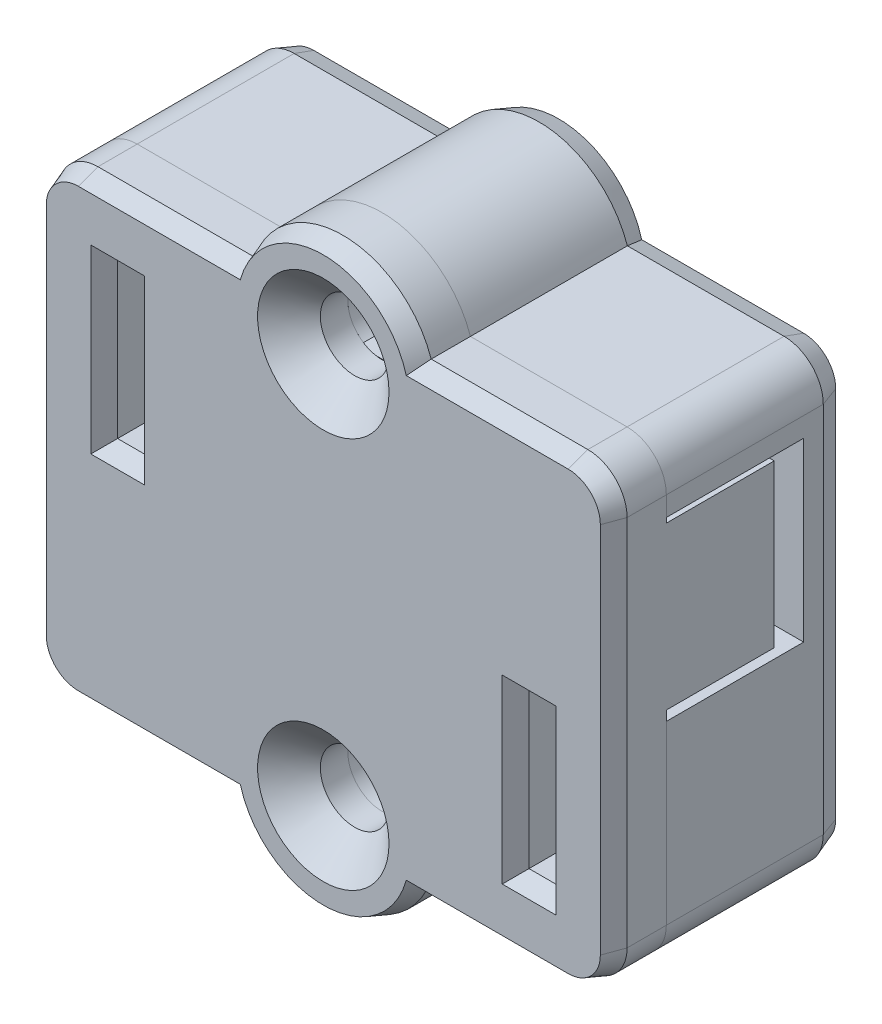
SolidWorks part; units mm, degrees
ref_plane "Спереди" through (0, 0, 0) normal (0, 0, 1) x (1, 0, 0)
ref_plane "Сверху" through (0, 0, 0) normal (0, 1, 0) x (1, 0, 0)
ref_plane "Справа" through (0, 0, 0) normal (1, 0, 0) x (0, 0, -1)
sketch "Sketch2" plane through (0, 0, 0) normal (0, 0, 1) x (1, 0, 0)
  line L1 (8.9024, -9.7858) -> (10.9024, -9.7858)
  line L2 (8.9024, -9.7858) -> (8.9024, -1.7858)
  line L3 (8.9024, -1.7858) -> (10.9024, -1.7858)
  line L4 (10.9024, -9.7858) -> (10.9024, -1.7858)
  line L5 (-10.0691, -0.7858) -> (-12.0691, -0.7858)
  line L6 (-10.0691, -0.7858) -> (-10.0691, 7.2142)
  line L7 (-10.0691, 7.2142) -> (-12.0691, 7.2142)
  line L8 (-12.0691, -0.7858) -> (-12.0691, 7.2142)
  dimension "D1" = 8
  dimension "D2" = 8
  dimension "D5" = 2
  dimension "D6" = 2
sketch "Sketch4" plane through (0, 0, 0) normal (0, 0, 1) x (1, 0, 0)
  line L0 (13.9024, 10.2142) -> (3.9167, 10.2142)
  line L1 (10.9024, -9.7858) -> (0.3699, -9.7858)
  line L2 (10.9024, -9.7858) -> (10.9024, 7.2142)
  line L3 (10.9024, 7.2142) -> (0.3699, 7.2142)
  line L4 (-12.0691, -9.7858) -> (-12.0691, 7.2142)
  line L5 (-15.0691, -12.7858) -> (-15.0691, 10.2142)
  line L6 (13.9024, -12.7858) -> (3.9167, -12.7858)
  line L7 (13.9024, -12.7858) -> (13.9024, 10.2142)
  line L8 (-0.5833, -11.1954) -> (-0.5833, 8.6818) construction
  line L9 (-12.0691, -1.2858) -> (-6.8964, -1.2858) construction
  line L10 (-1.5366, 7.2142) -> (-12.0691, 7.2142)
  line L11 (-5.0833, 10.2142) -> (-15.0691, 10.2142)
  line L12 (13.9024, 10.2142) -> (-15.0691, 10.2142) construction
  line L13 (-5.0833, -12.7858) -> (-15.0691, -12.7858)
  line L14 (13.9024, -12.7858) -> (-15.0691, -12.7858) construction
  line L15 (10.9024, 7.2142) -> (-12.0691, 7.2142) construction
  line L16 (-1.5366, -9.7858) -> (-12.0691, -9.7858)
  line L17 (10.9024, -9.7858) -> (-12.0691, -9.7858) construction
  arc A0 (0.3699, -9.7858) -> (-1.5366, -9.7858) centre (-0.5833, -11.2534) cw
  arc A1 (3.9167, 10.2142) -> (-5.0833, 10.2142) centre (-0.5833, 8.6818) ccw
  arc A2 (0.3699, 7.2142) -> (-1.5366, 7.2142) centre (-0.5833, 8.6818) ccw
  arc A3 (3.9167, -12.7858) -> (-5.0833, -12.7858) centre (-0.5833, -11.2534) cw
  point P12 (-0.5833, -1.2858)
  dimension "D2" = 3.5
  dimension "D1" = 3
extrude "Extrude3" add sketch "Sketch4" along normal blind 7
sketch "Sketch5" plane through (0, 7.2142, 0) normal (0, -1, 0) x (1, 0, 0)
  line L0 (-12.0691, 7) -> (-12.0691, 0) construction
  line L5 (0.3699, 7) -> (0.3699, 0)
  line L6 (0.3699, 0) -> (10.9024, 0)
  line L7 (10.9024, 0) -> (10.9024, 7)
  line L8 (-12.0691, 0) -> (10.9024, 0)
  line L9 (-12.0691, 7) -> (-12.0691, 0)
  line L10 (10.9024, 7) -> (0.3699, 7)
  line L11 (10.9024, 7) -> (-12.0691, 7)
  arc A0 (-12.0691, 7) -> (-5.0691, 0) centre (-5.0691, 7) ccw
  line M10 (0.3699, 0) -> (10.9024, 0)
  dimension "D1" = 0
extrude "Extrude4" add sketch "Sketch5" along normal blind 8 contours A0 M10 region at (-10.5055, 7.2142, 1.5636)
sketch "Sketch6" plane through (0, -9.7858, 0) normal (0, 1, 0) x (1, 0, 0)
  line L1 (10.9024, -7) -> (10.9024, 0) construction
  line L5 (0.3699, 0) -> (0.3699, -7)
  line L6 (10.9024, 0) -> (0.3699, 0)
  line L7 (0.3699, 0) -> (0.3699, -7)
  line L8 (10.9024, 0) -> (0.3699, 0)
  line L9 (10.9024, -7) -> (10.9024, 0)
  line L10 (0.3699, -7) -> (10.9024, -7)
  line L11 (0.3699, -7) -> (10.9024, -7)
  line L13 (10.9024, -7) -> (10.9024, 0)
  arc A0 (10.9024, -7) -> (3.9024, 0) centre (3.9024, -7) ccw
  line M8 (10.9024, -7) -> (10.9024, 0)
  line M10 (10.9024, 0) -> (0.3699, 0)
  dimension "D1" = 0
extrude "Extrude5" add sketch "Sketch6" along normal blind 8 contours A0 M8 M10 region at (9.3389, -9.7858, 1.5636)
sketch "Sketch7" plane through (0, 0, 0) normal (0, 0, -1) x (-1, 0, 0)
  line L6 (-13.9024, 10.2142) -> (-13.9024, -12.7858)
  line L7 (-13.9024, -12.7858) -> (-3.9167, -12.7858)
  line L8 (5.0833, -12.7858) -> (15.0691, -12.7858)
  line L9 (15.0691, -12.7858) -> (15.0691, 10.2142)
  line L10 (15.0691, 10.2142) -> (5.0833, 10.2142)
  line L11 (-3.9167, 10.2142) -> (-13.9024, 10.2142)
  line L12 (-13.9024, 10.2142) -> (-13.9024, -12.7858)
  line L13 (-13.9024, -12.7858) -> (-3.9167, -12.7858)
  line L14 (5.0833, -12.7858) -> (15.0691, -12.7858)
  line L15 (15.0691, -12.7858) -> (15.0691, 10.2142)
  line L16 (15.0691, 10.2142) -> (5.0833, 10.2142)
  line L17 (-3.9167, 10.2142) -> (-13.9024, 10.2142)
  circle A0 centre (0.5833, 8.6818) radius 1.75 construction
  circle A1 centre (0.5833, 8.6818) radius 1.75
  arc A2 (-3.9167, -12.7858) -> (5.0833, -12.7858) centre (0.5833, -11.2534) ccw
  arc A3 (5.0833, 10.2142) -> (-3.9167, 10.2142) centre (0.5833, 8.6818) ccw
  arc A4 (-3.9167, -12.7858) -> (5.0833, -12.7858) centre (0.5833, -11.2534) ccw
  arc A5 (5.0833, 10.2142) -> (-3.9167, 10.2142) centre (0.5833, 8.6818) ccw
  arc A7 (-0.3699, -9.7858) -> (1.5366, -9.7858) centre (0.5833, -11.2534) ccw construction
  circle A8 centre (0.5833, -11.2534) radius 1.75
  dimension "D1" = 0
extrude "Extrude6" add sketch "Sketch7" along normal blind 2
fillet "Fillet1" radius 2 4 edges at (-15.0691, -12.7858, 2.5) (13.9024, -12.7858, 2.5) (13.9024, 10.2142, 2.5) (-15.0691, 10.2142, 2.5)
sketch "Sketch9" plane through (-12.0691, 0, 0) normal (1, 0, 0) x (0, 0, -1)
  line L0 (0, -0.7858) -> (0, -9.7858)
  line L1 (0, -0.7858) -> (-7, -0.7858)
  line L3 (-7, -0.7858) -> (-7, -9.7858)
  line L4 (-7, -9.7858) -> (0, -9.7858)
extrude "Extrude8" cut sketch "Sketch9" against normal up to next contours L3 L4 L0 L1
sketch "Sketch10" plane through (10.9024, 0, 0) normal (-1, 0, 0) x (0, 0, 1)
  line L4 (0, -1.7858) -> (7, -1.7858)
  line L5 (7, -1.7858) -> (7, 7.2142)
  line L6 (7, 7.2142) -> (0, 7.2142)
  line L7 (0, 7.2142) -> (0, -1.7858)
  line L8 (0, -1.7858) -> (7, -1.7858)
  line L9 (7, -1.7858) -> (7, 7.2142)
  line L10 (7, 7.2142) -> (0, 7.2142)
  line L11 (0, 7.2142) -> (0, -1.7858)
  dimension "D1" = 0
extrude "Extrude9" cut sketch "Sketch10" against normal up to next
sketch "Sketch11" plane through (0, 7.2142, 0) normal (0, -1, 0) x (1, 0, 0)
  line L0 (13.9024, 0) -> (0.3699, 0) construction
  line L1 (3.9167, 7) -> (-5.0833, 7) construction
  line L2 (-0.5833, 1.9408) -> (3.0586, 1.9408)
  line L3 (3.0586, 1.9408) -> (3.0586, 0)
  line L4 (-4.2253, 0) -> (3.0586, 0)
  line L5 (0.3699, 0) -> (13.9024, 0)
  line L6 (13.9024, 0) -> (13.9024, 7)
  line L7 (13.9024, 7) -> (0.3699, 7)
  line L12 (0.3699, 7) -> (0.3699, 0)
  line L13 (0.3699, 7) -> (0.3699, 0)
  arc A0 (-4.2253, 0) -> (-0.5833, 1.9408) centre (-0.5833, -2.4468) cw
  point P7 (-0.5833, 7)
  dimension "D1" = 0
extrude "Extrude10" add sketch "Sketch11" along normal up to vertex (8 mm away) contours A0 L2 L3 L4 up to point (-5.0691, -0.7858, 0)
sketch "Sketch12" plane through (0, -9.7858, 0) normal (0, 1, 0) x (1, 0, 0)
  line L0 (-4.2253, 0) -> (-4.2253, -1.9408)
  line L1 (-4.2253, -1.9408) -> (-0.5833, -1.9408)
  line L2 (-4.2253, 0) -> (3.0586, 0)
  arc A0 (-4.2253, 0) -> (-0.5833, -1.9408) centre (-0.5833, 2.4468) ccw construction
  arc A1 (-0.5833, -1.9408) -> (3.0586, 0) centre (-1.4942, 4.1561) ccw
extrude "Extrude11" add sketch "Sketch12" along normal up to vertex (8 mm away) up to point (3.9024, -1.7858, 0)
sketch "Sketch13" plane through (0, -0.7858, 0) normal (0, -1, 0) x (1, 0, 0)
  line L3 (-4.2253, 0) -> (3.0586, 0)
  line L4 (3.0586, 0) -> (3.0586, 1.9408)
  line L5 (3.0586, 1.9408) -> (-0.5833, 1.9408)
  line L6 (-4.2253, 0) -> (3.0586, 0)
  line L7 (3.0586, 0) -> (3.0586, 1.9408)
  line L8 (3.0586, 1.9408) -> (-0.5833, 1.9408)
  arc A0 (-0.5833, 1.9408) -> (3.0586, 0) centre (-0.5833, -2.4468) cw
  arc A1 (-0.5833, 1.9408) -> (-4.2253, 0) centre (-0.5833, -2.4468) ccw
  arc A2 (-0.5833, 1.9408) -> (-4.2253, 0) centre (-0.5833, -2.4468) ccw
  arc M5 (-0.5833, 1.9408) -> (-4.2253, 0) centre (-0.5833, -2.4468) ccw
  line M6 (-4.2253, 0) -> (3.0586, 0)
  dimension "D1" = 0
extrude "Extrude12" add sketch "Sketch13" along normal up to vertex (1 mm away) contours A0 M5 M6 region at (-0.5833, -0.7858, 0.7932) up to point (3.0586, -1.7858, 0)
sketch "Sketch14" plane through (0, -9.7858, 0) normal (0, 1, 0) x (1, 0, 0)
  line L20 (-15.0691, -1.5) -> (-15.0691, -7)
  line L21 (-15.0691, -7) -> (9.4024, -7)
  line L28 (3.9024, -1.5) -> (3.6781, -1.5)
  line L29 (-6.8681, -1.5) -> (-15.0691, -1.5)
  line L30 (-5.7253, -3.4408) -> (-6.8681, -1.5)
  line L31 (-0.478, -3.4408) -> (-5.7253, -3.4408)
  arc A11 (9.4024, -7) -> (3.9024, -1.5) centre (3.9024, -7) ccw
  arc A12 (-0.478, -3.4408) -> (3.6781, -1.5) centre (-1.4942, 4.1561) ccw
extrude "Extrude13" add sketch "Sketch14" along normal blind 8.25 from offset 0.25 separate body
sketch "Sketch15" plane through (0, 7.2142, 0) normal (0, -1, 0) x (1, 0, 0)
  line L28 (-10.5691, 7) -> (13.9024, 7)
  line L29 (13.9024, 7) -> (13.9024, 1.5)
  line L36 (13.9024, 1.5) -> (4.5586, 1.5)
  line L37 (4.5586, 1.5) -> (4.5586, 3.4408)
  line L38 (4.5586, 3.4408) -> (-0.5833, 3.4408)
  line L39 (-4.9521, 1.5) -> (-5.0691, 1.5)
  arc A26 (-0.5833, 3.4408) -> (-4.9521, 1.5) centre (-0.5833, -2.4468) ccw
  arc A27 (-10.5691, 7) -> (-5.0691, 1.5) centre (-5.0691, 7) ccw
extrude "Extrude14" add sketch "Sketch15" along normal blind 8.25 from offset 0.25
sketch "Sketch16" plane through (0, 0, 7) normal (0, 0, 1) x (1, 0, 0)
  line L0 (-15.0691, 8.2142) -> (-15.0691, -10.7858)
  line L1 (13.9024, 8.2142) -> (13.9024, -10.7858)
  line L5 (-10.5691, -1.2858) -> (-12.0691, -1.2858)
  line L6 (-10.5691, -1.2858) -> (-10.5691, 7.2142)
  line L7 (0.3699, 7.2142) -> (13.9024, 7.2142)
  line L8 (13.9024, 7.2142) -> (13.9024, 8.2142)
  line L9 (11.9024, 10.2142) -> (3.9167, 10.2142)
  line L10 (-5.0833, 10.2142) -> (-13.0691, 10.2142)
  line L11 (-15.0691, 8.2142) -> (-15.0691, -0.7858)
  line L12 (-15.0691, -0.7858) -> (-12.0691, -0.7858)
  line L13 (-12.0691, -0.7858) -> (-12.0691, 7.2142)
  line L14 (-10.5691, 7.2142) -> (-12.0691, 7.2142)
  line L16 (11.9024, 10.2142) -> (3.9167, 10.2142)
  line L17 (-5.0833, 10.2142) -> (-13.0691, 10.2142)
  line L21 (13.9024, -1.7858) -> (10.9024, -1.7858)
  line L22 (10.9024, -1.7858) -> (10.9024, -9.7858)
  line L23 (10.9024, -9.7858) -> (0.3699, -9.7858)
  line L24 (-15.0691, -9.7858) -> (-15.0691, -10.7858)
  line L25 (-13.0691, -12.7858) -> (-5.0833, -12.7858)
  line L26 (3.9167, -12.7858) -> (11.9024, -12.7858)
  line L27 (13.9024, -10.7858) -> (13.9024, -1.7858)
  line L28 (-12.0691, -1.2858) -> (-12.0691, 7.2142)
  line L29 (9.4024, -1.2858) -> (9.4024, -9.5358) construction
  line L30 (9.4024, -1.2858) -> (10.9024, -1.2858)
  line L32 (-13.0691, -12.7858) -> (-5.0833, -12.7858)
  line L33 (3.9167, -12.7858) -> (11.9024, -12.7858)
  line L35 (9.4024, -1.2858) -> (9.4024, -9.7858)
  line L36 (9.4024, -9.7858) -> (10.9024, -9.7858)
  line L37 (10.9024, -1.2858) -> (10.9024, -9.7858)
  line L41 (-1.5366, -9.7858) -> (-15.0691, -9.7858)
  line L44 (-12.0691, 7.2142) -> (-1.5366, 7.2142)
  line L45 (-12.0691, 7.2142) -> (-1.5366, 7.2142)
  circle A0 centre (-0.5833, 8.6818) radius 1.75 construction
  circle A1 centre (-0.5833, 8.6818) radius 1.75
  arc A3 (13.9024, 8.2142) -> (11.9024, 10.2142) centre (11.9024, 8.2142) ccw
  arc A4 (3.9167, 10.2142) -> (-5.0833, 10.2142) centre (-0.5833, 8.6818) ccw
  arc A5 (-13.0691, 10.2142) -> (-15.0691, 8.2142) centre (-13.0691, 8.2142) ccw
  arc A6 (13.9024, 8.2142) -> (11.9024, 10.2142) centre (11.9024, 8.2142) ccw
  arc A7 (3.9167, 10.2142) -> (-5.0833, 10.2142) centre (-0.5833, 8.6818) ccw
  arc A8 (-13.0691, 10.2142) -> (-15.0691, 8.2142) centre (-13.0691, 8.2142) ccw
  arc A9 (-15.0691, -10.7858) -> (-13.0691, -12.7858) centre (-13.0691, -10.7858) ccw
  arc A10 (-1.5366, -9.7858) -> (0.3699, -9.7858) centre (-0.5833, -11.2534) ccw
  arc A11 (11.9024, -12.7858) -> (13.9024, -10.7858) centre (11.9024, -10.7858) ccw
  arc A12 (-15.0691, -10.7858) -> (-13.0691, -12.7858) centre (-13.0691, -10.7858) ccw
  arc A13 (-1.5366, -9.7858) -> (0.3699, -9.7858) centre (-0.5833, -11.2534) ccw
  arc A14 (11.9024, -12.7858) -> (13.9024, -10.7858) centre (11.9024, -10.7858) ccw
  circle A15 centre (-0.5833, -11.2534) radius 1.75
  arc A20 (0.3699, 7.2142) -> (-1.5366, 7.2142) centre (-0.5833, 8.6818) ccw
  arc A21 (0.3699, 7.2142) -> (-1.5366, 7.2142) centre (-0.5833, 8.6818) ccw
  arc A22 (-5.0833, -12.7858) -> (3.9167, -12.7858) centre (-0.5833, -11.2534) ccw
  arc A23 (-5.0833, -12.7858) -> (3.9167, -12.7858) centre (-0.5833, -11.2534) ccw
  line M21 (-15.0691, -9.5358) -> (9.4024, -9.5358)
  line M22 (9.4024, -9.5358) -> (9.4024, -1.2858)
  line M23 (9.4024, -1.2858) -> (13.9024, -1.2858)
  line M24 (13.9024, -1.2858) -> (13.9024, 6.9642)
  line M25 (13.9024, 6.9642) -> (-10.5691, 6.9642)
  line M26 (-10.5691, 6.9642) -> (-10.5691, -1.2858)
  line M27 (-10.5691, -1.2858) -> (-15.0691, -1.2858)
  line M28 (-15.0691, -1.2858) -> (-15.0691, -9.5358)
  dimension "D1" = 0
  dimension "D2" = 0
extrude "Extrude15" add sketch "Sketch16" along normal blind 3 contours L17 A8 L0 L28 L14 L45 A1 L1 A6 L16 A7 M27 M25 | L32 A23 L33 A14 L1 L37 L36 L35 A15 A13 L0 A12 M23 M21 | A15 A1 M21 M22 M23 M24 M25 M26 M27 M28 | A1 L45 L6 M25 region at (-3.1563, 8.1031, 7) region at (-13.5691, -1.0358, 7) region at (-0.5833, -1.2858, 7) region at (-8.1758, -9.6599, 7) region at (1.9897, -10.6747, 7) region at (-5.9253, 7.0879, 7) region at (4.7586, -9.6595, 7) region at (7.0091, 7.0883, 7) region at (12.4024, -1.5358, 7)
sketch "Sketch18" plane through (0, 0, 10) normal (0, 0, 1) x (1, 0, 0)
  line L1 (-12.0691, -1.2858) -> (-10.0691, -1.2858)
  line L2 (-12.0691, -1.2858) -> (-12.0691, 7.2142)
  line L3 (-12.0691, 7.2142) -> (-10.0691, 7.2142)
  line L4 (-10.0691, -1.2858) -> (-10.0691, 7.2142)
  line L5 (10.9024, -9.7858) -> (8.9024, -9.7858)
  line L6 (10.9024, -9.7858) -> (10.9024, -1.2858)
  line L7 (10.9024, -1.2858) -> (8.9024, -1.2858)
  line L8 (8.9024, -9.7858) -> (8.9024, -1.2858)
  dimension "D1" = 2
  dimension "D2" = 2
extrude "Extrude16" cut sketch "Sketch18" against normal up to next (6.6056 mm away)
chamfer "Chamfer3" distance 1.6 angle 45 2 edges at (1.1667, -11.2534, 10) (1.1667, 8.6818, 10)
chamfer "Chamfer1" distance 1 angle 20 14 edges at (-9.0762, 10.2142, -2) (-14.4833, 9.6284, -2) (-15.0691, -1.2858, -2) (-14.4833, -12.2, -2) (-9.0762, -12.7858, -2) (-0.5833, -16.0072, -2) (7.9095, -12.7858, -2) (13.3166, -12.2, -2) (13.9024, -1.2858, -2) (13.3166, 9.6284, -2) (7.9095, 10.2142, -2) (-0.5833, 13.4356, -2) (-2.3333, 8.6818, -2) (-2.3333, -11.2534, -2) first distance on face at (-9.0762, 10.2142, 2.5) first distance on face at (-14.2762, 9.4213, 2.5) first distance on face at (-15.0691, -3.2858, 3) first distance on face at (-14.2762, -11.9929, 2.5) first distance on face at (-9.0762, -12.7858, 2.5) first distance on face at (-0.5833, -14.3965, 2.5) first distance on face at (7.9095, -12.7858, 2.5) first distance on face at (13.1095, -11.9929, 2.5) first distance on face at (13.9024, 0.7142, 3) first distance on face at (13.1095, 9.4213, 2.5) first distance on face at (7.9095, 10.2142, 2.5) first distance on face at (-0.5833, 11.8249, 2.5) first distance on face at (-0.5833, 7.7034, 2.9628) first distance on face at (-0.5833, -10.275, 2.9434)
chamfer "Chamfer2" distance 1 angle 20 20 edges at (-11.0691, 7.2142, 10) (-12.0691, 2.9642, 10) (-10.0691, 2.9642, 10) (-11.0691, -1.2858, 10) (9.9024, -9.7858, 10) (8.9024, -5.5358, 10) (9.9024, -1.2858, 10) (10.9024, -5.5358, 10) (7.9095, 10.2142, 10) (13.3166, 9.6284, 10) (13.9024, -1.2858, 10) (13.3166, -12.2, 10) (-0.5833, -16.0072, 10) (7.9095, -12.7858, 10) (-9.0762, -12.7858, 10) (-14.4833, -12.2, 10) (-15.0691, -1.2858, 10) (-14.4833, 9.6284, 10) (-9.0762, 10.2142, 10) (-0.5833, 13.4356, 10) first distance on face at (-11.0691, 7.2142, 8.5) first distance on face at (-12.0691, 1.9017, 8.875) first distance on face at (-10.0691, 4.2975, 7.2362) first distance on face at (-11.3971, -1.2858, 5.4612) first distance on face at (9.9024, -9.7858, 8.5) first distance on face at (8.9024, -6.8691, 7.2362) first distance on face at (10.0255, -1.2858, 5.4478) first distance on face at (10.9024, -4.4733, 8.875) first distance on face at (7.9095, 10.2142, 8.5) first distance on face at (13.1095, 9.4213, 8.5) first distance on face at (13.9024, 1.4486, 5.6875) first distance on face at (13.1095, -11.9929, 8.5) first distance on face at (-0.5833, -14.3965, 8.5) first distance on face at (7.9095, -12.7858, 8.5) first distance on face at (-9.0762, -12.7858, 8.5) first distance on face at (-14.2762, -11.9929, 8.5) first distance on face at (-15.0691, -2.6764, 5.6875) first distance on face at (-14.2762, 9.4213, 8.5) first distance on face at (-9.0762, 10.2142, 8.5) first distance on face at (-0.5833, 11.8249, 8.5)
move or copy body "Body-Move/Copy1" [suppressed] bodies to move or copy 118 copy no rotation origin (13.9024, 0, 7) rotation axis (0, 1, 0) rotation angle 180
move or copy body "Body-Move/Copy2" [suppressed] bodies to move or copy 118 copy no translate (2, 0, -6)
